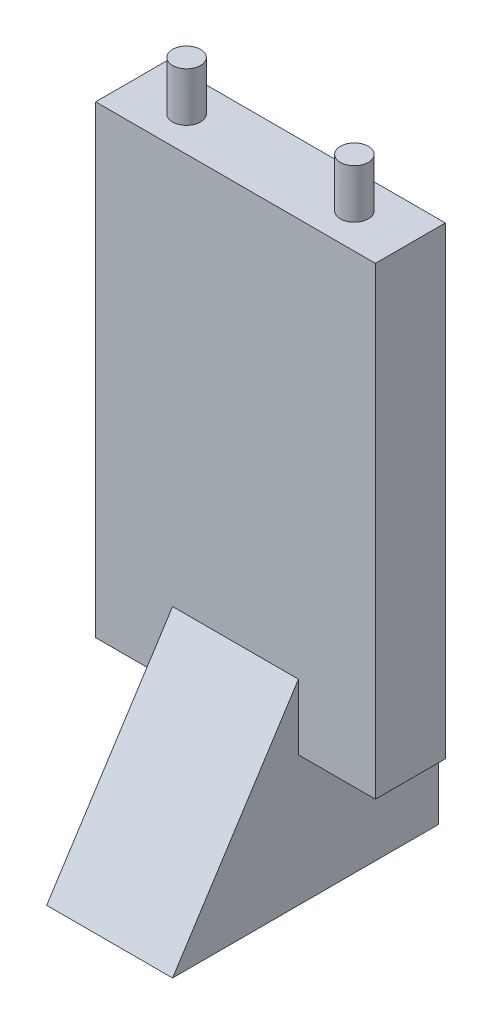
SolidWorks part; units mm, degrees
ref_plane "Front Plane" through (0, 0, 0) normal (0, 0, 1) x (1, 0, 0)
ref_plane "Top Plane" through (0, 0, 0) normal (0, 1, 0) x (1, 0, 0)
ref_plane "Right Plane" through (0, 0, 0) normal (1, 0, 0) x (0, 0, -1)
sketch "Sketch1" plane through (0, 0, 0) normal (0, 1, 0) x (1, 0, 0)
  line L1 (0, -10.671) -> (-21.342, -10.671) construction
  line L7 (-21.342, -10.671) -> (80.258, -10.671)
  line L8 (-21.342, -10.671) -> (-21.342, 14.729)
  line L9 (-21.342, 14.729) -> (80.258, 14.729)
  line L10 (80.258, -10.671) -> (80.258, 14.729)
extrude "Boss-Extrude1" add sketch "Sketch1" along normal blind 215.9 contours L9 L10 L7 L8
sketch "Sketch2" plane through (0, 215.9, 0) normal (0, 1, 0) x (1, 0, 0)
  line L0 (29.458, 14.729) -> (29.458, -10.671) construction
  line L1 (-21.342, 14.729) -> (80.258, 14.729) construction
  line L2 (-21.342, -10.671) -> (80.258, -10.671) construction
  line L3 (29.458, 2.029) -> (15.488, 2.029) construction
  line L4 (29.458, 2.029) -> (-1.022, 2.029) construction
  line L5 (29.458, 2.029) -> (59.938, 2.029) construction
  circle A1 centre (-1.022, 2.029) radius 5.08
  circle A2 centre (59.938, 2.029) radius 5.08
  dimension "D1" = 10.16
  dimension "D2" = 10.16
extrude "Boss-Extrude2" add sketch "Sketch2" along normal blind 17.78
sketch "Sketch3" plane through (0, 0, 10.671) normal (0, 0, 1) x (1, 0, 0)
  line L1 (-21.342, 0) -> (6.598, 0)
  line L2 (-21.342, 0) -> (-21.342, 47.3461)
  line L3 (-21.342, 47.3461) -> (6.598, 47.3461)
  line L4 (6.598, 0) -> (6.598, 47.3461)
  line L5 (80.258, 0) -> (52.318, 0)
  line L6 (80.258, 0) -> (80.258, 47.3461)
  line L7 (80.258, 47.3461) -> (52.318, 47.3461)
  line L8 (52.318, 0) -> (52.318, 47.3461)
extrude "Cut-Extrude1" cut sketch "Sketch3" against normal blind 27.686
sketch "Sketch9" plane through (0, 0, 10.671) normal (0, 0, 1) x (1, 0, 0)
  line L1 (6.598, 0) -> (52.318, 0)
  line L2 (6.598, 0) -> (6.598, 71.12)
  line L3 (6.598, 71.12) -> (52.318, 71.12)
  line L4 (52.318, 0) -> (52.318, 71.12)
extrude "Boss-Extrude5" add sketch "Sketch9" along normal blind 45.72
sketch "Sketch10" plane through (52.318, 0, 0) normal (1, 0, 0) x (0, 0, -1)
  line L0 (-56.391, 71.12) -> (-10.671, 71.12)
  line L1 (-10.671, 71.12) -> (-56.391, 0)
  line L2 (-56.391, 0) -> (-56.391, 71.12)
extrude "Cut-Extrude4" cut sketch "Sketch10" against normal blind 45.72
sketch "Sketch11" plane through (0, 0, -14.729) normal (0, 0, -1) x (-1, 0, 0)
  line L0 (-52.318, 47.3461) -> (-52.318, 70.9794)
  line L1 (-6.598, 47.3461) -> (-6.598, 70.9794)
  line L2 (-6.598, 70.9794) -> (-52.318, 70.9794)
  line L3 (-52.318, 47.3461) -> (-52.318, 0)
  line L4 (-52.318, 0) -> (-6.598, 0)
  line L5 (-6.598, 0) -> (-6.598, 47.3461)
extrude "Boss-Extrude6" add sketch "Sketch11" along normal blind 25.4
sketch "Sketch12" plane through (0, 0, 0) normal (0, -1, 0) x (1, 0, 0)
  line L0 (29.458, -40.129) -> (29.458, 3.5534) construction
  line L1 (52.318, -40.129) -> (6.598, -40.129) construction
  circle A0 centre (29.458, -21.079) radius 3.175
  circle A1 centre (29.458, 17.021) radius 3.175
  dimension "D1" = 6.35
  dimension "D2" = 6.35
  dimension "D3" = 38.1
  dimension "D4" = 19.05
extrude "Cut-Extrude5" cut sketch "Sketch12" against normal blind 12.7
